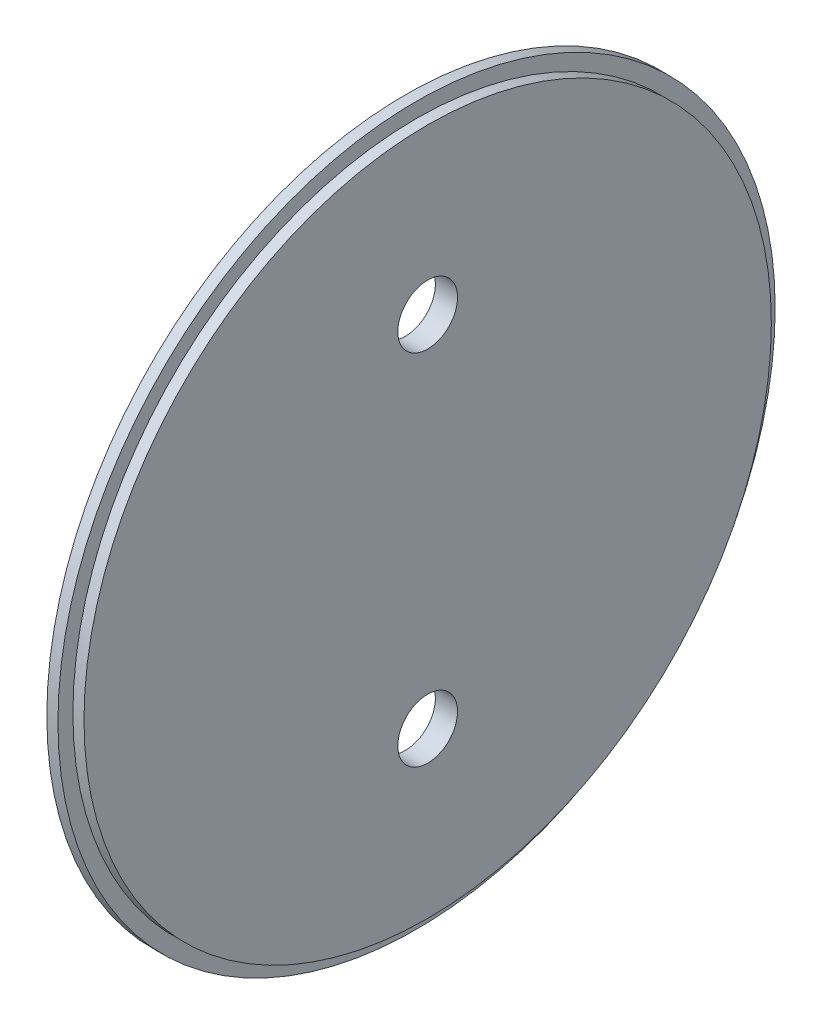
SolidWorks part; units mm, degrees
ref_plane "Front Plane" through (0, 0, 0) normal (1, 0, 0) x (0, 1, 0)
ref_plane "Top Plane" through (0, 0, 0) normal (0, 0, 1) x (0, 1, 0)
ref_plane "Right Plane" through (0, 0, 0) normal (0, 1, 0) x (-1, 0, 0)
sketch "Sketch1" plane through (0, 0, 0) normal (1, 0, 0) x (0, 1, 0)
  circle A0 centre (0, 0) radius 38.1
  dimension "D1" = 76.2
extrude "Boss-Extrude1" add sketch "Sketch1" along normal blind 1.1811
sketch "Sketch2" plane through (1.1811, 0, 0) normal (1, 0, 0) x (0, 1, 0)
  circle A0 centre (0, 0) radius 36.5125
  dimension "D1" = 73.025
extrude "Boss-Extrude2" add sketch "Sketch2" along normal blind 1.1811
sketch "Sketch3" plane through (0, 0, 0) normal (-1, 0, 0) x (0, -1, 0)
  circle A1 centre (19.05, 0) radius 3.175
  circle A2 centre (-19.05, 0) radius 3.175
  point P0 (0, 0)
  point P7 (-11.8468, 0.4811)
  point P8 (-11.8468, 0.4811)
  point P9 (0, 0)
  dimension "D1" = 19.05
  dimension "D2" = 6.35
  dimension "D3" = 6.35
  dimension "D4" = 19.05
extrude "Cut-Extrude1" cut sketch "Sketch3" against normal through all
